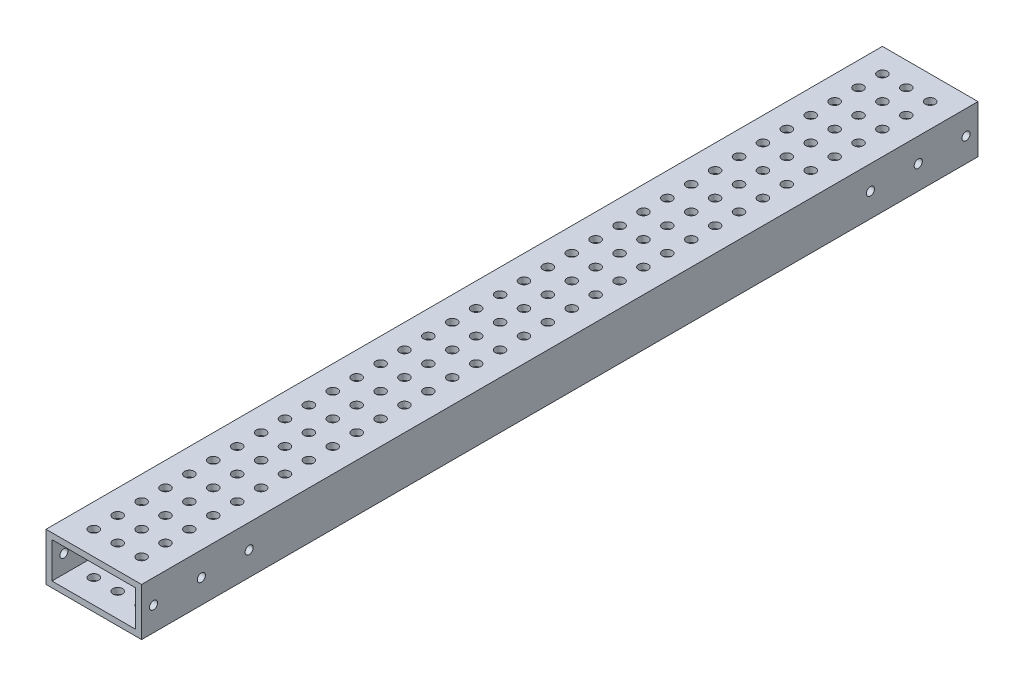
SolidWorks part; units mm, degrees
ref_plane "Front Plane" through (0, 0, 0) normal (0, 0, 1) x (1, 0, 0)
ref_plane "Top Plane" through (0, 0, 0) normal (0, 1, 0) x (1, 0, 0)
ref_plane "Right Plane" through (0, 0, 0) normal (1, 0, 0) x (0, 0, -1)
sketch "Sketch1" plane through (0, 0, 0) normal (0, 0, 1) x (1, 0, 0)
  line L0 (-22.225, 9.525) -> (22.225, 9.525)
  line L1 (-25.4, 12.7) -> (25.4, 12.7)
  line L2 (-25.4, 12.7) -> (-25.4, -12.7)
  line L3 (-25.4, -12.7) -> (25.4, -12.7)
  line L4 (25.4, 12.7) -> (25.4, -12.7)
  line L5 (22.225, 9.525) -> (22.225, -9.525)
  line L6 (-22.225, -9.525) -> (22.225, -9.525)
  line L7 (-22.225, 9.525) -> (-22.225, -9.525)
  line L8 (-25.4, 12.7) -> (25.4, -12.7) construction
  line L9 (25.4, 12.7) -> (-25.4, -12.7) construction
  dimension "D1" = 50.8
  dimension "D2" = 25.4
  dimension "D3" = 3.175
extrude "Boss-Extrude1" add sketch "Sketch1" along normal mid plane 444.5
sketch "Sketch2" plane through (0, 12.7, 0) normal (0, 1, 0) x (1, 0, 0)
  line L0 (25.4, -222.25) -> (-25.4, -222.25) construction
  line L1 (-25.4, -222.25) -> (-25.4, 222.25) construction
  line L2 (-12.7, -209.55) -> (0, -209.55) construction
  line L3 (0, -209.55) -> (12.7, -209.55) construction
  circle A0 centre (0, -209.55) radius 2.5527
  circle A1 centre (12.7, -209.55) radius 2.5527
  circle A2 centre (-12.7, -209.55) radius 2.5527
  circle A3 centre (-12.7, -196.85) radius 2.5527
  circle A4 centre (0, -196.85) radius 2.5527
  circle A5 centre (12.7, -196.85) radius 2.5527
  circle A6 centre (-12.7, -184.15) radius 2.5527
  circle A7 centre (0, -184.15) radius 2.5527
  circle A8 centre (12.7, -184.15) radius 2.5527
  circle A9 centre (-12.7, -171.45) radius 2.5527
  circle A10 centre (0, -171.45) radius 2.5527
  circle A11 centre (12.7, -171.45) radius 2.5527
  circle A12 centre (-12.7, -158.75) radius 2.5527
  circle A13 centre (0, -158.75) radius 2.5527
  circle A14 centre (12.7, -158.75) radius 2.5527
  circle A15 centre (-12.7, -146.05) radius 2.5527
  circle A16 centre (0, -146.05) radius 2.5527
  circle A17 centre (12.7, -146.05) radius 2.5527
  circle A18 centre (-12.7, -133.35) radius 2.5527
  circle A19 centre (0, -133.35) radius 2.5527
  circle A20 centre (12.7, -133.35) radius 2.5527
  circle A21 centre (-12.7, -120.65) radius 2.5527
  circle A22 centre (0, -120.65) radius 2.5527
  circle A23 centre (12.7, -120.65) radius 2.5527
  circle A24 centre (-12.7, -107.95) radius 2.5527
  circle A25 centre (0, -107.95) radius 2.5527
  circle A26 centre (12.7, -107.95) radius 2.5527
  circle A27 centre (-12.7, -95.25) radius 2.5527
  circle A28 centre (0, -95.25) radius 2.5527
  circle A29 centre (12.7, -95.25) radius 2.5527
  circle A30 centre (-12.7, -82.55) radius 2.5527
  circle A31 centre (0, -82.55) radius 2.5527
  circle A32 centre (12.7, -82.55) radius 2.5527
  circle A33 centre (-12.7, -69.85) radius 2.5527
  circle A34 centre (0, -69.85) radius 2.5527
  circle A35 centre (12.7, -69.85) radius 2.5527
  circle A36 centre (-12.7, -57.15) radius 2.5527
  circle A37 centre (0, -57.15) radius 2.5527
  circle A38 centre (12.7, -57.15) radius 2.5527
  circle A39 centre (-12.7, -44.45) radius 2.5527
  circle A40 centre (0, -44.45) radius 2.5527
  circle A41 centre (12.7, -44.45) radius 2.5527
  circle A42 centre (-12.7, -31.75) radius 2.5527
  circle A43 centre (0, -31.75) radius 2.5527
  circle A44 centre (12.7, -31.75) radius 2.5527
  circle A45 centre (-12.7, -19.05) radius 2.5527
  circle A46 centre (0, -19.05) radius 2.5527
  circle A47 centre (12.7, -19.05) radius 2.5527
  circle A48 centre (-12.7, -6.35) radius 2.5527
  circle A49 centre (0, -6.35) radius 2.5527
  circle A50 centre (12.7, -6.35) radius 2.5527
  circle A51 centre (-12.7, 6.35) radius 2.5527
  circle A52 centre (0, 6.35) radius 2.5527
  circle A53 centre (12.7, 6.35) radius 2.5527
  circle A54 centre (-12.7, 19.05) radius 2.5527
  circle A55 centre (0, 19.05) radius 2.5527
  circle A56 centre (12.7, 19.05) radius 2.5527
  circle A57 centre (-12.7, 31.75) radius 2.5527
  circle A58 centre (0, 31.75) radius 2.5527
  circle A59 centre (12.7, 31.75) radius 2.5527
  circle A60 centre (-12.7, 44.45) radius 2.5527
  circle A61 centre (0, 44.45) radius 2.5527
  circle A62 centre (12.7, 44.45) radius 2.5527
  circle A63 centre (-12.7, 57.15) radius 2.5527
  circle A64 centre (0, 57.15) radius 2.5527
  circle A65 centre (12.7, 57.15) radius 2.5527
  circle A66 centre (-12.7, 69.85) radius 2.5527
  circle A67 centre (0, 69.85) radius 2.5527
  circle A68 centre (12.7, 69.85) radius 2.5527
  circle A69 centre (-12.7, 82.55) radius 2.5527
  circle A70 centre (0, 82.55) radius 2.5527
  circle A71 centre (12.7, 82.55) radius 2.5527
  circle A72 centre (-12.7, 95.25) radius 2.5527
  circle A73 centre (0, 95.25) radius 2.5527
  circle A74 centre (12.7, 95.25) radius 2.5527
  circle A75 centre (-12.7, 107.95) radius 2.5527
  circle A76 centre (0, 107.95) radius 2.5527
  circle A77 centre (12.7, 107.95) radius 2.5527
  circle A78 centre (-12.7, 120.65) radius 2.5527
  circle A79 centre (0, 120.65) radius 2.5527
  circle A80 centre (12.7, 120.65) radius 2.5527
  circle A81 centre (-12.7, 133.35) radius 2.5527
  circle A82 centre (0, 133.35) radius 2.5527
  circle A83 centre (12.7, 133.35) radius 2.5527
  circle A84 centre (-12.7, 146.05) radius 2.5527
  circle A85 centre (0, 146.05) radius 2.5527
  circle A86 centre (12.7, 146.05) radius 2.5527
  circle A87 centre (-12.7, 158.75) radius 2.5527
  circle A88 centre (0, 158.75) radius 2.5527
  circle A89 centre (12.7, 158.75) radius 2.5527
  circle A90 centre (-12.7, 171.45) radius 2.5527
  circle A91 centre (0, 171.45) radius 2.5527
  circle A92 centre (12.7, 171.45) radius 2.5527
  circle A93 centre (-12.7, 184.15) radius 2.5527
  circle A94 centre (0, 184.15) radius 2.5527
  circle A95 centre (12.7, 184.15) radius 2.5527
  circle A96 centre (-12.7, 196.85) radius 2.5527
  circle A97 centre (0, 196.85) radius 2.5527
  circle A98 centre (12.7, 196.85) radius 2.5527
  circle A99 centre (-12.7, 209.55) radius 2.5527
  circle A100 centre (0, 209.55) radius 2.5527
  circle A101 centre (12.7, 209.55) radius 2.5527
  circle A108 centre (-12.7, 234.95) radius 2.5527 [skipped]
  circle A109 centre (0, 234.95) radius 2.5527 [skipped]
  circle A110 centre (12.7, 234.95) radius 2.5527 [skipped]
  circle A111 centre (-12.7, 222.25) radius 2.5527 [skipped]
  circle A112 centre (0, 222.25) radius 2.5527 [skipped]
  circle A113 centre (12.7, 222.25) radius 2.5527 [skipped]
  dimension "D2" = 5.1054
  dimension "D4" = 12.7
  dimension "D1" = 12.7
  dimension "D3" = 25.4
  dimension "D5" = 36
extrude "Cut-Extrude1" cut sketch "Sketch2" against normal through all
sketch "Sketch3" plane through (25.4, 0, 0) normal (1, 0, 0) x (0, 0, -1)
  line L0 (-222.25, -12.7) -> (-222.25, 12.7) construction
  line L1 (-222.25, 12.7) -> (222.25, 12.7) construction
  line L2 (222.25, -12.7) -> (222.25, 12.7) construction
  circle A0 centre (-215.9, 0) radius 2.159
  circle A1 centre (-190.5, 0) radius 2.159
  circle A2 centre (-165.1, 0) radius 2.159
  circle A3 centre (215.9, 0) radius 2.159
  circle A4 centre (190.5, 0) radius 2.159
  circle A5 centre (165.1, 0) radius 2.159
  dimension "D2" = 4.318
  dimension "D9" = 4.318
  dimension "D1" = 6.35
  dimension "D3" = 12.7
  dimension "D4" = 31.75
  dimension "D5" = 12.7
  dimension "D6" = 57.15
  dimension "D7" = 12.7
  dimension "D8" = 6.35
  dimension "D10" = 12.7
  dimension "D11" = 31.75
  dimension "D12" = 57.15
  dimension "D13" = 12.7
  dimension "D14" = 12.7
extrude "Cut-Extrude2" cut sketch "Sketch3" against normal through all
